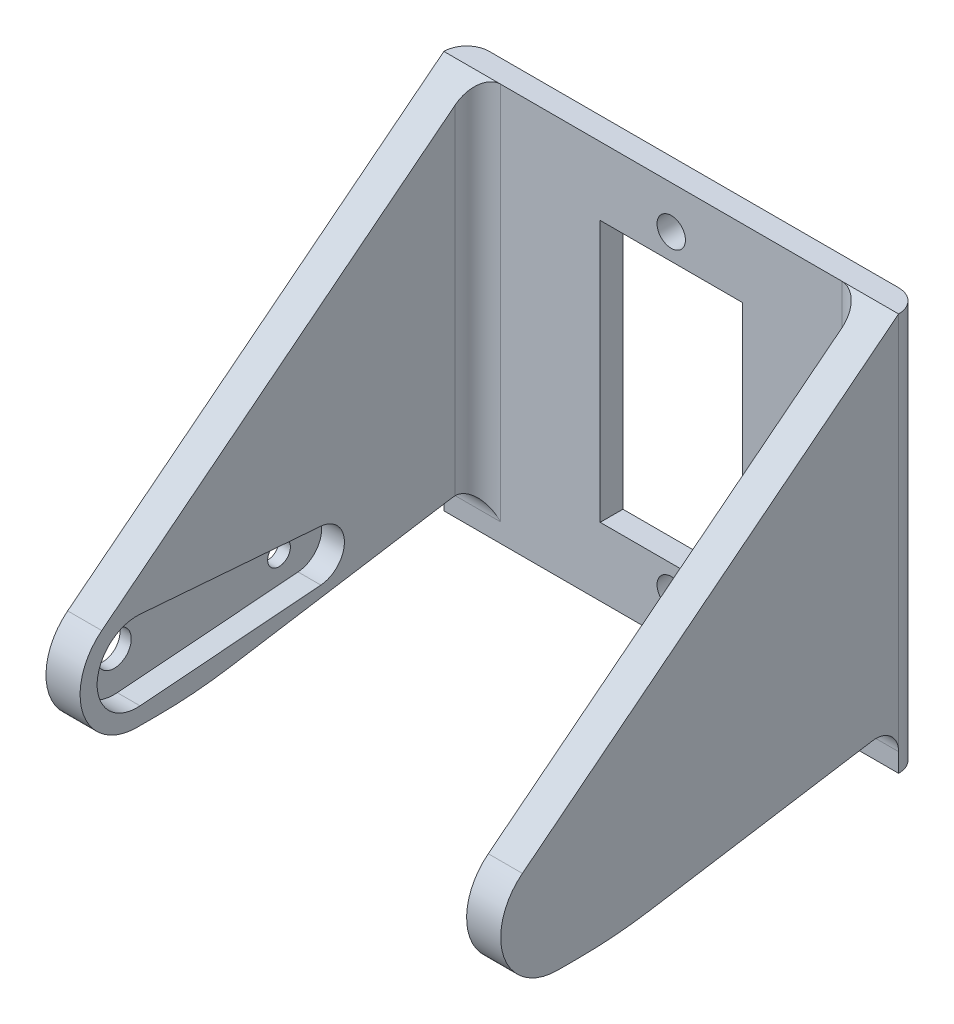
SolidWorks part; units mm, degrees
ref_plane "前视基准面" through (0, 0, 0) normal (0, 0, 1) x (1, 0, 0)
ref_plane "上视基准面" through (0, 0, 0) normal (0, 1, 0) x (1, 0, 0)
ref_plane "右视基准面" through (0, 0, 0) normal (1, 0, 0) x (0, 0, -1)
sketch "草图1" plane through (0, 0, 0) normal (0, 0, 1) x (1, 0, 0)
  line L1 (20, -17.5) -> (-20, -17.5)
  line L2 (20, -17.5) -> (20, 17.5)
  line L3 (20, 17.5) -> (-20, 17.5)
  line L4 (-20, -17.5) -> (-20, 17.5)
  line L5 (20, -17.5) -> (-20, 17.5) construction
  line L6 (20, 17.5) -> (-20, -17.5) construction
  line L7 (-6.25, 11.5) -> (6.25, 11.5)
  line L8 (-6.25, 11.5) -> (-6.25, -11.5)
  line L9 (-6.25, -11.5) -> (6.25, -11.5)
  line L10 (6.25, 11.5) -> (6.25, -11.5)
  line L11 (-6.25, 11.5) -> (6.25, -11.5) construction
  line L12 (-6.25, -11.5) -> (6.25, 11.5) construction
  circle A0 centre (0, 13.75) radius 1.25
  circle A1 centre (0, -13.75) radius 1.25
  point P0 (0, 0)
  point P6 (0, 0)
  dimension "D5" = 2.5
  dimension "D6" = 2.25
  dimension "D7" = 2.25
  dimension "D1" = 35
  dimension "D2" = 40
  dimension "D3" = 12.5
  dimension "D4" = 23
extrude "凸台-拉伸1" add sketch "草图1" along normal blind 2
sketch "草图2" plane through (-20, 0, 0) normal (-1, 0, 0) x (0, 0, 1)
  line L0 (2, -17.5) -> (32, -17.5)
  line L1 (35.0942, -8.5724) -> (2, 17.5)
  line L2 (2, 17.5) -> (2, -17.5)
  arc A0 (35.0942, -8.5724) -> (32, -17.5) centre (32, -12.5) cw
  dimension "D2" = 5
  dimension "D1" = 30
extrude "凸台-拉伸2" add sketch "草图2" against normal blind 3
sketch "草图3" plane through (-17, 0, 0) normal (1, 0, 0) x (0, 0, -1)
  line L0 (-31.7266, -9.0107) -> (-15.8242, -10.2569)
  line L1 (-31.7266, -15.9893) -> (-15.8242, -14.7431)
  arc A0 (-31.7266, -9.0107) -> (-31.7266, -15.9893) centre (-32, -12.5) ccw
  circle A1 centre (-16, -12.5) radius 2.25
  arc A3 (-35.0942, -8.5724) -> (-32, -17.5) centre (-32, -12.5) ccw construction
  dimension "D1" = 16
  dimension "D3" = 4.5
  dimension "D4" = 7
extrude "切除-拉伸1" cut sketch "草图3" against normal blind 2 contours A1 L0 A0 L1 | A1 L0 region at (-17, -12.5, 26.8195) region at (-17, -12.5, 16)
mirror "镜向3" about plane through (0, 0, 0) normal (1, 0, 0) of "凸台-拉伸2"
sketch "草图4" plane through (17, 0, 0) normal (-1, 0, 0) x (0, 0, 1)
  circle A0 centre (32, -12.5) radius 2.5
  arc A1 (32, -17.5) -> (35.0942, -8.5724) centre (32, -12.5) ccw construction
  dimension "D1" = 5
extrude "凸台-拉伸3" add sketch "草图4" along normal blind 1.5
sketch "草图5" plane through (20, 0, 0) normal (1, 0, 0) x (0, 0, -1)
  line L0 (-2, -17.5) -> (-2, -13.5)
  line L1 (-32, -17.5) -> (0, -17.5) construction
  line L2 (-2, -13.5) -> (-27, -17.5)
  line L3 (-27, -17.5) -> (-2, -17.5)
  dimension "D1" = 2
  dimension "D2" = 4
  dimension "D3" = 25
extrude "切除-拉伸2" cut sketch "草图5" against normal through all
fillet "圆角1" radius 40 2 edges at (-18.5, -17.5, 27) (18.5, -17.5, 27)
sketch "草图6" plane through (-19, 0, 0) normal (1, 0, 0) x (0, 0, -1)
  circle A0 centre (-32, -12.5) radius 1.5
  arc A1 (-31.7266, -9.0107) -> (-31.7266, -15.9893) centre (-32, -12.5) ccw construction
  dimension "D1" = 3
extrude "切除-拉伸3" cut sketch "草图6" against normal blind 10
sketch "草图7" plane through (-19, 0, 0) normal (1, 0, 0) x (0, 0, -1)
  line L0 (-32, -12.5) -> (-17.5, -12.5) construction
  circle A0 centre (-17.5, -12.5) radius 1
  circle A1 centre (-32, -12.5) radius 1.5 construction
  dimension "D1" = 2
  dimension "D2" = 14.5
extrude "切除-拉伸4" cut sketch "草图7" against normal blind 10
fillet "圆角2" radius 2 6 edges at (17, 2, 2) (-17, 2, 2) (20, 0, 0) (-20, 0, 0) (18.5, -13.5, 2) (-18.5, -13.5, 2)
